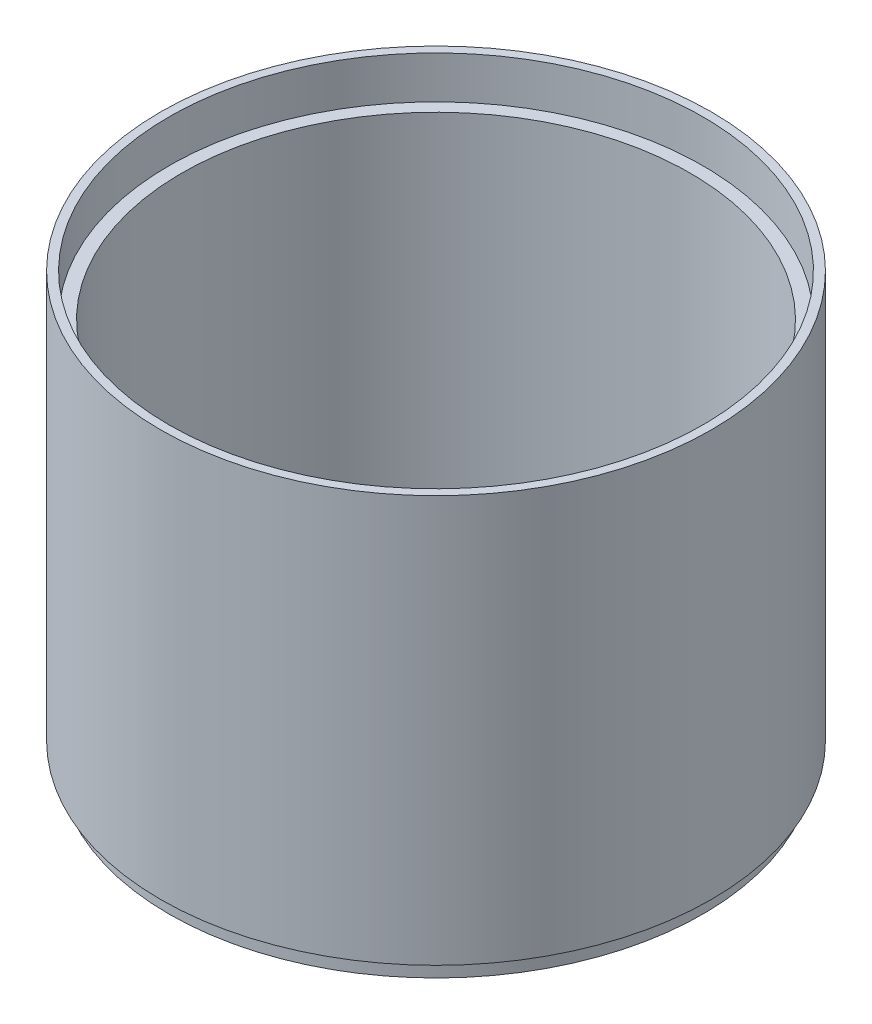
SolidWorks part; units mm, degrees
material "HYPALON"
ref_plane "Front Plane" through (0, 0, 0) normal (0, 0, 1) x (1, 0, 0)
ref_plane "Top Plane" through (0, 0, 0) normal (0, 1, 0) x (1, 0, 0)
ref_plane "Right Plane" through (0, 0, 0) normal (1, 0, 0) x (0, 0, -1)
sketch "Szkic1" plane through (0, 0, 0) normal (0, 0, 1) x (1, 0, 0)
  line L0 (-63, 0) -> (0, 0)
  line L1 (-63, 0) -> (-60, 0)
  line L2 (-63, 0) -> (-63, 4)
  line L3 (-63, 4) -> (-65, 4)
  line L4 (-65, 4) -> (-65, 28.5618)
  line L5 (-60, 0) -> (-60, 90)
  line L6 (-60, 90) -> (-63, 90)
  line L7 (-63, 90) -> (-63, 100)
  line L8 (-63, 100) -> (-65, 100)
  line L9 (-65, 100) -> (-65, 28.5618)
  line L10 (0, 35.541) -> (0, 0)
  dimension "D1" = 65
  dimension "D2" = 4
  dimension "D3" = 2
  dimension "D4" = 10
  dimension "D5" = 2
  dimension "D6" = 5
  dimension "D7" = 60
  dimension "D8" = 90
revolve "Obrót1" add sketch "Szkic1" angle 360 about L10 region at (-62.539, 47.9091, 0)
